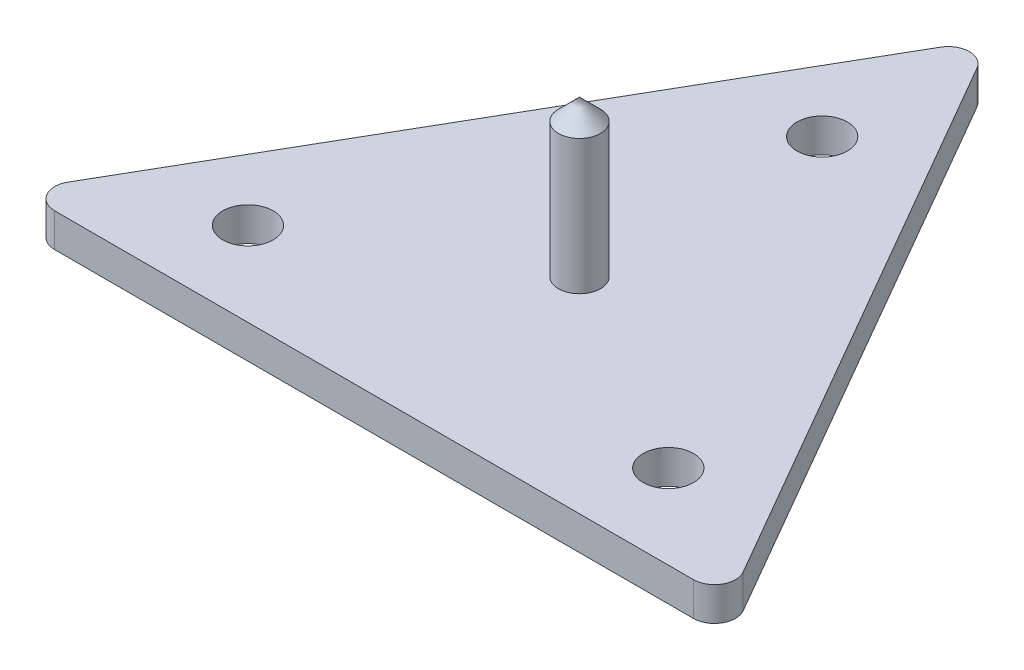
SolidWorks part; units mm, degrees
ref_plane "Front Plane" through (0, 0, 0) normal (0, 0, 1) x (1, 0, 0)
ref_plane "Top Plane" through (0, 0, 0) normal (0, 1, 0) x (1, 0, 0)
ref_plane "Right Plane" through (0, 0, 0) normal (1, 0, 0) x (0, 0, -1)
sketch "Sketch1" plane through (0, 0, 0) normal (0, 1, 0) x (1, 0, 0)
  line L0 (-115.6863, 120.509) -> (-65.6863, 207.1115)
  line L1 (-65.6863, 207.1115) -> (-15.6863, 120.509)
  line L2 (-15.6863, 120.509) -> (-115.6863, 120.509)
  line L3 (-65.6863, 247.1115) -> (18.9547, 100.509)
  line L4 (18.9547, 100.509) -> (-150.3273, 100.509)
  line L5 (-150.3273, 100.509) -> (-65.6863, 247.1115)
  dimension "D1" = 100
  dimension "D2" = 20
extrude "Boss-Extrude1" add sketch "Sketch1" along normal blind 8 contours L3 L4 L5
sketch "Sketch4" plane through (0, 8, 0) normal (0, 1, 0) x (1, 0, 0)
  line L6 (-65.6863, 207.1115) -> (-115.6863, 120.509)
  line L7 (-115.6863, 120.509) -> (-15.6863, 120.509)
  line L8 (-15.6863, 120.509) -> (-65.6863, 207.1115)
  line L9 (-65.6863, 207.1115) -> (-115.6863, 120.509)
  line L10 (-115.6863, 120.509) -> (-15.6863, 120.509)
  line L11 (-15.6863, 120.509) -> (-65.6863, 207.1115)
  dimension "D1" = 20
hole_wizard "Ø12.0 (12) Diameter Hole1" positions "Sketch5" profile "Sketch7" hole size "Ø12.0" standard "ISO" end condition through all
sketch "Sketch5" plane through (0, 8, 0) normal (0, 1, 0) x (1, 0, 0)
  point P0 (-65.6863, 207.1115)
  point P3 (-115.6863, 120.509)
  point P6 (-15.6863, 120.509)
sketch "Sketch7" plane through (-65.6863, 8, -207.1115) normal (1, 0, 0) x (0, 0, 1)
  line L0 (0, 0) -> (0, 8)
  line L1 (0, 8) -> (6, 8)
  line L2 (6, 8) -> (6, 0)
  line L5 (6, 0) -> (0, 0)
  line L11 (0, -6.35) -> (0, 107.95) construction
  dimension "Thru Hole Dia." = 12
  dimension "Thru Hole Depth" = 8
sketch "Sketch8" plane through (0, 0, 0) normal (0, -1, 0) x (-1, 0, 0)
  circle A0 centre (65.6863, 149.3765) radius 97.735 construction
  circle A1 centre (65.6863, 149.3765) radius 5
extrude "Boss-Extrude2" add sketch "Sketch8" against normal blind 45
fillet "Fillet1" radius 5 3 edges at (-150.3273, 4, -100.509) (-65.6863, 4, -247.1115) (18.9547, 4, -100.509)
chamfer "Chamfer1" distance 5 angle 45 1 edges at (-65.6863, 45, -154.3765)
equation "\"TRIANGLE_SIDE\"= 100"
equation "\"D1@Sketch1\"=\"TRIANGLE_SIDE\""
equation "\"TRIANGLE_OFFSET\"=20"
equation "\"D2@Sketch1\"=\"TRIANGLE_OFFSET\""
equation "\"TRIANGLE_Z\"= 8"
equation "\"D1@Boss-Extrude1\"=\"TRIANGLE_Z\""
equation "\"D1@Sketch4\"=\"TRIANGLE_OFFSET\""
